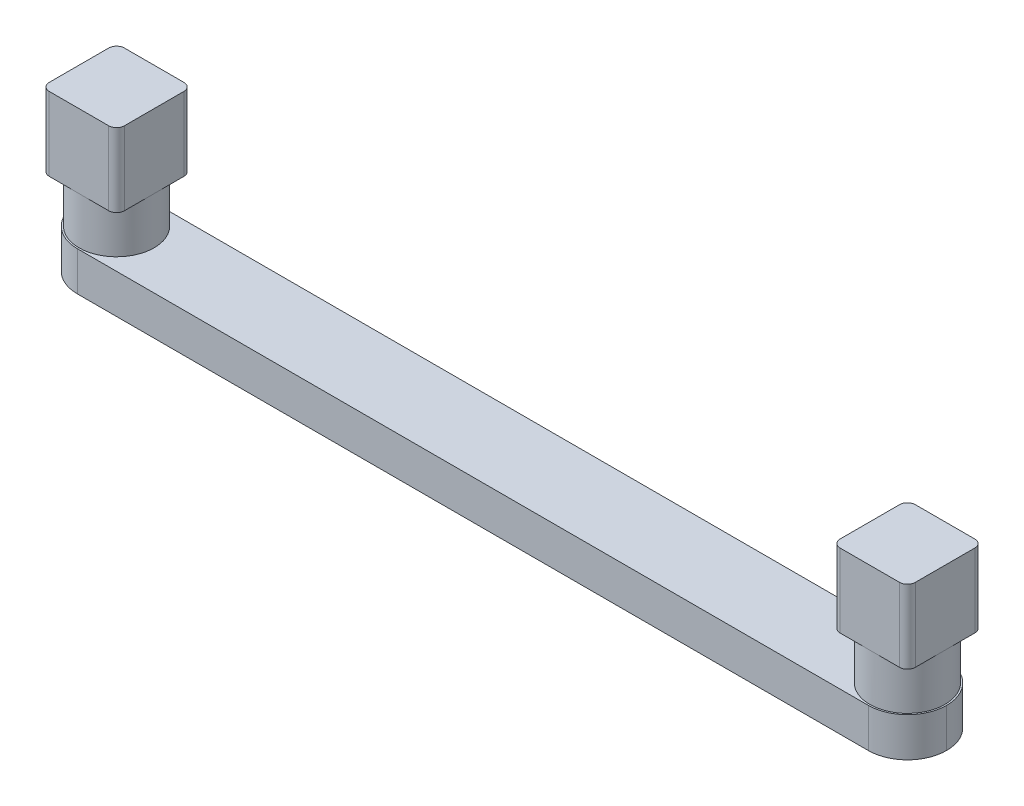
SolidWorks part; units mm, degrees
ref_plane "Front Plane" through (0, 0, 0) normal (0, 0, 1) x (1, 0, 0)
ref_plane "Top Plane" through (0, 0, 0) normal (0, 1, 0) x (1, 0, 0)
ref_plane "Right Plane" through (0, 0, 0) normal (1, 0, 0) x (0, 0, -1)
sketch "Sketch1" plane through (0, 0, 0) normal (0, 1, 0) x (1, 0, 0)
  line L0 (0, 0) -> (0, 58.3413) construction
  line L1 (-35.2425, -3.175) -> (35.2425, -3.175)
  line L2 (-35.2425, -3.175) -> (-35.2425, 3.175)
  line L3 (-35.2425, 3.175) -> (35.2425, 3.175)
  line L4 (35.2425, -3.175) -> (35.2425, 3.175)
  line L5 (-35.2425, -3.175) -> (35.2425, 3.175) construction
  line L6 (-35.2425, 3.175) -> (35.2425, -3.175) construction
  line L7 (0, 0) -> (32.0675, 0) construction
  point P0 (0, 0)
  dimension "D1" = 32.0675
  dimension "D2" = 3.175
  dimension "D3" = 6.35
extrude "Boss-Extrude1" add sketch "Sketch1" along normal blind 3.175
sketch "Sketch2" plane through (0, 3.175, 0) normal (0, 1, 0) x (1, 0, 0)
  line L0 (0, 0) -> (32.0675, 0) construction
  circle A0 centre (32.0675, 0) radius 3.048
  dimension "D2" = 6.096
  dimension "D1" = 32.0675
extrude "Boss-Extrude2" add sketch "Sketch2" along normal blind 3.81
sketch "Sketch3" plane through (0, 6.985, 0) normal (0, 1, 0) x (1, 0, 0)
  line L1 (29.0195, -3.048) -> (35.1155, -3.048)
  line L2 (29.0195, -3.048) -> (29.0195, 3.048)
  line L3 (29.0195, 3.048) -> (35.1155, 3.048)
  line L4 (35.1155, -3.048) -> (35.1155, 3.048)
  line L5 (29.0195, -3.048) -> (35.1155, 3.048) construction
  line L6 (29.0195, 3.048) -> (35.1155, -3.048) construction
  point P0 (32.0675, 0)
  dimension "D1" = 6.096
  dimension "D2" = 6.096
extrude "Boss-Extrude3" add sketch "Sketch3" along normal blind 5.969
fillet "Fillet1" radius 3.175 4 edges at (-35.2425, 1.5875, 3.175) (-35.2425, 1.5875, -3.175) (35.2425, 1.5875, 3.175) (35.2425, 1.5875, -3.175)
fillet "Fillet2" radius 0.635 4 edges at (35.1155, 9.9695, 3.048) (29.0195, 9.9695, 3.048) (29.0195, 9.9695, -3.048) (35.1155, 9.9695, -3.048)
mirror "Mirror1" about plane through (0, 0, 0) normal (1, 0, 0) of "Fillet2", "Boss-Extrude3", "Boss-Extrude2"
